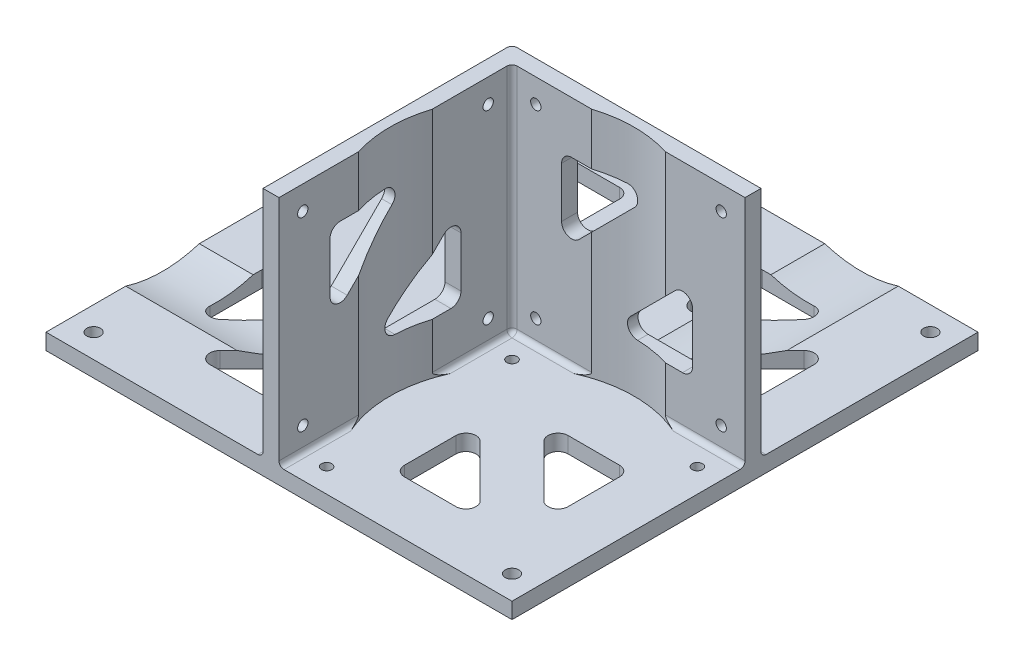
SolidWorks part; units mm, degrees
ref_plane "Front Plane" through (0, 0, 0) normal (0, 0, 1) x (1, 0, 0)
ref_plane "Top Plane" through (0, 0, 0) normal (0, 1, 0) x (1, 0, 0)
ref_plane "Right Plane" through (0, 0, 0) normal (1, 0, 0) x (0, 0, -1)
sketch "Sketch1" plane through (0, 0, 0) normal (0, 1, 0) x (1, 0, 0)
  line L0 (-41.525, 46.25) -> (-41.525, -46.25) construction
  line L1 (-46.25, -46.25) -> (46.25, -46.25)
  line L2 (-46.25, -46.25) -> (-46.25, 46.25)
  line L3 (-46.25, 46.25) -> (46.25, 46.25)
  line L4 (46.25, -46.25) -> (46.25, 46.25)
  line L5 (-46.25, -46.25) -> (46.25, 46.25) construction
  line L6 (-46.25, 46.25) -> (46.25, -46.25) construction
  line L7 (-46.25, -41.525) -> (46.25, -41.525) construction
  line L8 (41.525, -46.25) -> (41.525, 46.25) construction
  line L9 (-46.25, 41.525) -> (46.25, 41.525) construction
  circle A0 centre (-41.525, -41.525) radius 1.35
  circle A1 centre (-41.525, 41.525) radius 1.35
  circle A2 centre (41.525, 41.525) radius 1.35
  circle A3 centre (41.525, -41.525) radius 1.35
  point P0 (0, 0)
  dimension "D7" = 2.7
  dimension "D8" = 2.7
  dimension "D9" = 2.7
  dimension "D10" = 2.7
  dimension "D1" = 92.5
  dimension "D2" = 92.5
  dimension "D3" = 4.725
  dimension "D4" = 4.725
  dimension "D5" = 4.725
  dimension "D6" = 4.725
extrude "Base Plate" add sketch "Sketch1" along normal blind 3.175
sketch "Sketch2" plane through (0, 3.175, 0) normal (0, 1, 0) x (1, 0, 0)
  line L0 (0, 0) -> (46.25, 0)
  line L1 (46.25, -46.25) -> (46.25, 46.25) construction
  line L2 (0, 0) -> (0, -46.25)
  line L3 (-46.25, -46.25) -> (46.25, -46.25) construction
  line L4 (-3.175, -46.25) -> (-3.175, 3.175)
  line L7 (-3.175, 3.175) -> (46.25, 3.175)
  line L8 (-3.175, -46.25) -> (0, -46.25)
  line L9 (46.25, 0) -> (46.25, 3.175)
  dimension "D1" = 46.25
  dimension "D2" = 3.175
  dimension "D3" = 3.175
extrude "L-Bracket" add sketch "Sketch2" along normal blind 46.25
sketch "Sketch3" plane through (0, 3.175, 0) normal (0, 1, 0) x (1, 0, 0)
  line L0 (0, 0) -> (46.25, -46.25) construction
  line L1 (0, -46.25) -> (46.25, 0) construction
  line L5 (0, -46.25) -> (0, 0) construction
  circle A0 centre (23.125, -23.125) radius 21.625 construction
  circle A2 centre (41.525, -4.725) radius 0.2
  circle A3 centre (4.725, -4.725) radius 0.2
  circle A4 centre (4.725, -41.525) radius 0.2
  dimension "D1" = 43.25
  dimension "D4" = 4.725
extrude "RW Holes" cut sketch "Sketch3" against normal through all
sketch "Sketch7" plane through (0, 0, 0) normal (0, 0, 1) x (1, 0, 0)
  line L0 (0, 3.175) -> (46.25, 49.425) construction
  line L1 (0, 49.425) -> (46.25, 3.175) construction
  line L2 (46.25, 49.425) -> (46.25, 3.175) construction
  line L3 (0, 3.175) -> (46.25, 3.175) construction
  circle A0 centre (23.125, 26.3) radius 21.625 construction
  circle A1 centre (41.525, 7.9) radius 0.2
  circle A2 centre (4.725, 7.9) radius 0.2
  circle A3 centre (4.725, 44.7) radius 0.2
  circle A4 centre (41.525, 44.7) radius 0.2
  dimension "D1" = 43.25
  dimension "D2" = 0.4
  dimension "D3" = 4
  dimension "D4" = 4.725
  dimension "D5" = 41.525
  dimension "D6" = 4.725
  dimension "D8" = 46.25
extrude "RW Holes 2" cut sketch "Sketch7" against normal through all
sketch "Sketch8" plane through (0, 0, 0) normal (1, 0, 0) x (0, 0, -1)
  line L0 (-46.25, 49.425) -> (0, 3.175) construction
  line L1 (-46.25, 3.175) -> (0, 49.425) construction
  line L2 (-46.25, 3.175) -> (0, 3.175) construction
  circle A0 centre (-23.125, 26.3) radius 21.625 construction
  circle A1 centre (-41.525, 7.9) radius 0.2
  circle A2 centre (-41.525, 44.7) radius 0.2
  circle A3 centre (-4.725, 44.7) radius 0.2
  circle A4 centre (-4.725, 7.9) radius 0.2
  dimension "D1" = 43.25
  dimension "D4" = 0.4
  dimension "D2" = 4
  dimension "D3" = 4.725
  dimension "D5" = 41.525
  dimension "D6" = 4.725
extrude "RW Holes 3" cut sketch "Sketch8" against normal blind 45
sketch "Sketch10" plane through (0, 0, 0) normal (0, -1, 0) x (1, 0, 0)
  line L0 (-46.25, 46.25) -> (46.25, -46.25) construction
  line L1 (21.9291, 15.6133) -> (32.1447, 25.8289)
  line L2 (-46.25, -46.25) -> (46.25, 46.25) construction
  line L3 (35.559, 24.4147) -> (35.559, 14.1991)
  line L4 (33.559, 12.1991) -> (23.3433, 12.1991)
  line L5 (46.25, 46.25) -> (46.25, -46.25) construction
  line L6 (24.4147, 35.559) -> (14.1991, 35.559)
  line L7 (15.6133, 21.9291) -> (25.8289, 32.1447)
  line L8 (12.1991, 33.559) -> (12.1991, 23.3433)
  line L9 (35.559, -24.4147) -> (35.559, -14.1991)
  line L10 (33.559, -12.1991) -> (23.3433, -12.1991)
  line L11 (21.9291, -15.6133) -> (32.1447, -25.8289)
  line L12 (12.1991, -33.559) -> (12.1991, -23.3433)
  line L13 (15.6133, -21.9291) -> (25.8289, -32.1447)
  line L14 (24.4147, -35.559) -> (14.1991, -35.559)
  line L15 (-24.4147, -35.559) -> (-14.1991, -35.559)
  line L16 (-12.1991, -33.559) -> (-12.1991, -23.3433)
  line L17 (-15.6133, -21.9291) -> (-25.8289, -32.1447)
  line L18 (-33.559, -12.1991) -> (-23.3433, -12.1991)
  line L19 (-21.9291, -15.6133) -> (-32.1447, -25.8289)
  line L20 (-35.559, -24.4147) -> (-35.559, -14.1991)
  line L21 (-35.559, 24.4147) -> (-35.559, 14.1991)
  line L22 (-33.559, 12.1991) -> (-23.3433, 12.1991)
  line L23 (-21.9291, 15.6133) -> (-32.1447, 25.8289)
  line L24 (-12.1991, 33.559) -> (-12.1991, 23.3433)
  line L25 (-15.6133, 21.9291) -> (-25.8289, 32.1447)
  line L26 (-24.4147, 35.559) -> (-14.1991, 35.559)
  arc A0 (35.559, 14.1991) -> (33.559, 12.1991) centre (33.559, 14.1991) cw
  arc A1 (32.1447, 25.8289) -> (35.559, 24.4147) centre (33.559, 24.4147) cw
  arc A2 (21.9291, 15.6133) -> (23.3433, 12.1991) centre (23.3433, 14.1991) ccw
  arc A3 (25.8289, 32.1447) -> (24.4147, 35.559) centre (24.4147, 33.559) ccw
  arc A4 (14.1991, 35.559) -> (12.1991, 33.559) centre (14.1991, 33.559) ccw
  arc A5 (15.6133, 21.9291) -> (12.1991, 23.3433) centre (14.1991, 23.3433) cw
  arc A6 (35.559, -14.1991) -> (33.559, -12.1991) centre (33.559, -14.1991) ccw
  arc A7 (21.9291, -15.6133) -> (23.3433, -12.1991) centre (23.3433, -14.1991) cw
  arc A8 (32.1447, -25.8289) -> (35.559, -24.4147) centre (33.559, -24.4147) ccw
  arc A9 (15.6133, -21.9291) -> (12.1991, -23.3433) centre (14.1991, -23.3433) ccw
  arc A10 (14.1991, -35.559) -> (12.1991, -33.559) centre (14.1991, -33.559) cw
  arc A11 (25.8289, -32.1447) -> (24.4147, -35.559) centre (24.4147, -33.559) cw
  arc A12 (-14.1991, -35.559) -> (-12.1991, -33.559) centre (-14.1991, -33.559) ccw
  arc A13 (-15.6133, -21.9291) -> (-12.1991, -23.3433) centre (-14.1991, -23.3433) cw
  arc A14 (-25.8289, -32.1447) -> (-24.4147, -35.559) centre (-24.4147, -33.559) ccw
  arc A15 (-21.9291, -15.6133) -> (-23.3433, -12.1991) centre (-23.3433, -14.1991) ccw
  arc A16 (-35.559, -14.1991) -> (-33.559, -12.1991) centre (-33.559, -14.1991) cw
  arc A17 (-32.1447, -25.8289) -> (-35.559, -24.4147) centre (-33.559, -24.4147) cw
  arc A18 (-35.559, 14.1991) -> (-33.559, 12.1991) centre (-33.559, 14.1991) ccw
  arc A19 (-21.9291, 15.6133) -> (-23.3433, 12.1991) centre (-23.3433, 14.1991) cw
  arc A20 (-32.1447, 25.8289) -> (-35.559, 24.4147) centre (-33.559, 24.4147) ccw
  arc A21 (-15.6133, 21.9291) -> (-12.1991, 23.3433) centre (-14.1991, 23.3433) ccw
  arc A22 (-14.1991, 35.559) -> (-12.1991, 33.559) centre (-14.1991, 33.559) cw
  arc A23 (-25.8289, 32.1447) -> (-24.4147, 35.559) centre (-24.4147, 33.559) cw
  point P18 (35.559, 29.2431)
  point P21 (18.5149, 12.1991)
  dimension "D4" = 2
  dimension "D1" = 10.691
  dimension "D2" = 27.7351
  dimension "D3" = 17.0069
  dimension "D6" = 10.691
  dimension "D7" = 58.4491
  dimension "D5" = 4
extrude "WR1" cut sketch "Sketch10" against normal blind 45
sketch "Sketch11" plane through (0, 0, 0) normal (1, 0, 0) x (0, 0, -1)
  line L0 (-46.25, 49.425) -> (0, 3.175) construction
  line L1 (-46.25, 3.175) -> (0, 49.425) construction
  line L2 (-36.1242, 37.2992) -> (-36.1242, 27.2939)
  line L3 (-32.71, 25.8797) -> (-22.7047, 35.885)
  line L4 (-34.1242, 39.2992) -> (-24.1189, 39.2992)
  line L5 (-10.1258, 15.3008) -> (-10.1258, 25.3061)
  line L6 (-23.5453, 16.715) -> (-13.54, 26.7203)
  line L7 (-12.1258, 13.3008) -> (-22.1311, 13.3008)
  circle A0 centre (-4.725, 44.7) radius 0.2 construction
  arc A1 (-22.7047, 35.885) -> (-24.1189, 39.2992) centre (-24.1189, 37.2992) ccw
  arc A2 (-36.1242, 37.2992) -> (-34.1242, 39.2992) centre (-34.1242, 37.2992) cw
  arc A3 (-36.1242, 27.2939) -> (-32.71, 25.8797) centre (-34.1242, 27.2939) ccw
  arc A4 (-13.54, 26.7203) -> (-10.1258, 25.3061) centre (-12.1258, 25.3061) cw
  arc A5 (-12.1258, 13.3008) -> (-10.1258, 15.3008) centre (-12.1258, 15.3008) ccw
  arc A6 (-22.1311, 13.3008) -> (-23.5453, 16.715) centre (-22.1311, 15.3008) cw
  point P19 (-19.2905, 39.2992)
  point P22 (-36.1242, 39.2992)
  point P25 (-36.1242, 22.4655)
  dimension "D3" = 2
  dimension "D1" = 16.8337
  dimension "D2" = 14.5655
extrude "WR2" cut sketch "Sketch11" against normal blind 10
sketch "Sketch12" plane through (0, 0, 0) normal (0, 0, 1) x (1, 0, 0)
  line L0 (-0.2859, 49.2555) -> (45.9641, 3.0055) construction
  line L1 (-0.2859, 3.0055) -> (45.9641, 49.2555) construction
  line L2 (9.8399, 37.1297) -> (9.8399, 27.1244)
  line L3 (13.2541, 25.7102) -> (23.2594, 35.7154)
  line L4 (11.8399, 39.1297) -> (21.8451, 39.1297)
  line L5 (35.8382, 15.1313) -> (35.8382, 25.1365)
  line L6 (22.4188, 16.5455) -> (32.424, 26.5508)
  line L7 (33.8382, 13.1313) -> (23.833, 13.1313)
  arc A1 (23.2594, 35.7154) -> (21.8451, 39.1297) centre (21.8451, 37.1297) ccw
  arc A2 (9.8399, 37.1297) -> (11.8399, 39.1297) centre (11.8399, 37.1297) cw
  arc A3 (9.8399, 27.1244) -> (13.2541, 25.7102) centre (11.8399, 27.1244) ccw
  arc A4 (32.424, 26.5508) -> (35.8382, 25.1365) centre (33.8382, 25.1365) cw
  arc A5 (33.8382, 13.1313) -> (35.8382, 15.1313) centre (33.8382, 15.1313) ccw
  arc A6 (23.833, 13.1313) -> (22.4188, 16.5455) centre (23.833, 15.1313) cw
  circle A7 centre (4.725, 44.7) radius 0.2 construction
  point P19 (26.6736, 39.1297)
  point P22 (9.8399, 39.1297)
  point P25 (9.8399, 22.296)
  dimension "D3" = 2
  dimension "D1" = 16.8337
  dimension "D2" = 5.1149
  dimension "D4" = 17.6938
  dimension "D5" = 41.2391
  dimension "D6" = 4.5555
extrude "WR3" cut sketch "Sketch12" against normal blind 10
fillet "Fillet1" radius 1 6 edges at (0, 26.3, 0) (23.125, 3.175, 0) (0, 3.175, 23.125) (-3.175, 26.3, -3.175) (21.5375, 3.175, -3.175) (-3.175, 3.175, 21.5375)
hole_wizard "Tap Drill for M2.5x0.45 Tap4" positions "3DSketch2" profile "Sketch14" hole size "M2.5x0.45" standard "ANSI Metric" end condition through all
sketch3d "3DSketch2"
  line L0 (41.525, 0, 4.725) -> (41.525, 3.175, 4.725) construction
  line L1 (4.725, 0, 4.725) -> (4.725, 3.175, 4.725) construction
  line L2 (4.725, 0, 41.525) -> (4.725, 3.175, 41.525) construction
  point P0 (41.525, 3.175, 4.725)
  point P4 (4.725, 3.175, 4.725)
  point P8 (4.725, 3.175, 41.525)
sketch "Sketch14" plane through (41.525, 3.175, 4.725) normal (1, 0, 0) x (0, 0, 1)
  line L0 (0, 0) -> (0, 3.175)
  line L1 (0, 3.175) -> (1.025, 3.175)
  line L2 (1.025, 3.175) -> (1.025, 0)
  line L5 (1.025, 0) -> (0, 0)
  line L11 (0, -6.35) -> (0, 107.95) construction
  dimension "Thru Hole Dia." = 2.05
  dimension "Thru Hole Depth" = 3.175
hole_wizard "Tap Drill for M2.5x0.45 Tap5" positions "3DSketch3" profile "Sketch15" hole size "M2.5x0.45" standard "ANSI Metric" end condition through all
sketch3d "3DSketch3"
  line L0 (41.525, 44.7, -3.175) -> (41.525, 44.7, 0) construction
  line L1 (41.525, 7.9, -3.175) -> (41.525, 7.9, 0) construction
  line L2 (4.725, 7.9, -3.175) -> (4.725, 7.9, 0) construction
  line L3 (4.725, 44.7, -3.175) -> (4.725, 44.7, 0) construction
  point P0 (41.525, 44.7, 0)
  point P4 (41.525, 7.9, 0)
  point P8 (4.725, 7.9, 0)
  point P12 (4.725, 44.7, 0)
sketch "Sketch15" plane through (41.525, 44.7, 0) normal (1, 0, 0) x (0, -1, 0)
  line L0 (0, 0) -> (0, 46.25)
  line L1 (0, 46.25) -> (1.025, 46.25)
  line L2 (1.025, 46.25) -> (1.025, 0)
  line L5 (1.025, 0) -> (0, 0)
  line L11 (0, -6.35) -> (0, 107.95) construction
  dimension "Thru Hole Dia." = 2.05
  dimension "Thru Hole Depth" = 46.25
hole_wizard "Tap Drill for M2.5x0.45 Tap6" positions "3DSketch4" profile "Sketch16" hole size "M2.5x0.45" standard "ANSI Metric" end condition through all
sketch3d "3DSketch4"
  line L0 (-3.175, 44.7, 4.725) -> (0, 44.7, 4.725) construction
  line L1 (-3.175, 44.7, 41.525) -> (0, 44.7, 41.525) construction
  line L2 (-3.175, 7.9, 41.525) -> (0, 7.9, 41.525) construction
  line L3 (-3.175, 7.9, 4.725) -> (0, 7.9, 4.725) construction
  point P0 (-3.175, 44.7, 4.725)
  point P4 (-3.175, 44.7, 41.525)
  point P8 (-3.175, 7.9, 41.525)
  point P12 (-3.175, 7.9, 4.725)
sketch "Sketch16" plane through (-3.175, 44.7, 4.725) normal (0, 1, 0) x (0, 0, 1)
  line L0 (0, 0) -> (0, 49.425)
  line L1 (0, 49.425) -> (1.025, 49.425)
  line L2 (1.025, 49.425) -> (1.025, 0)
  line L5 (1.025, 0) -> (0, 0)
  line L11 (0, -6.35) -> (0, 107.95) construction
  dimension "Thru Hole Dia." = 2.05
  dimension "Thru Hole Depth" = 49.425
sketch "Sketch18" plane through (0, 49.425, 0) normal (0, 1, 0) x (1, 0, 0)
  line L0 (41.525, -41.525) -> (4.725, -4.725) construction
  line L1 (41.525, -4.725) -> (4.725, -41.525) construction
  circle A0 centre (23.125, -23.125) radius 24.25
extrude "Cut-Extrude1" cut sketch "Sketch18" against normal up to surface (46.25 mm away) up to face at (41.525, 3.175, 5.75)
sketch "Sketch19" plane through (0, 0, -46.25) normal (0, 0, -1) x (-1, 0, 0)
  line L0 (-41.525, 44.7) -> (-4.725, 7.9) construction
  line L1 (-4.725, 44.7) -> (-41.525, 7.9) construction
  circle A0 centre (-23.125, 26.3) radius 24.25
extrude "Cut-Extrude2" cut sketch "Sketch19" against normal up to surface (43.075 mm away) contours A0 up to face at (42.55, 44.7, -3.175)
sketch "Sketch20" plane through (-46.25, 0, 0) normal (-1, 0, 0) x (0, 0, 1)
  line L0 (4.725, 44.7) -> (41.525, 7.9) construction
  line L1 (41.525, 44.7) -> (4.725, 7.9) construction
  circle A0 centre (23.125, 26.3) radius 24.25
extrude "Cut-Extrude3" cut sketch "Sketch20" against normal up to surface (43.075 mm away) up to face at (-3.175, 44.7, 5.75)
